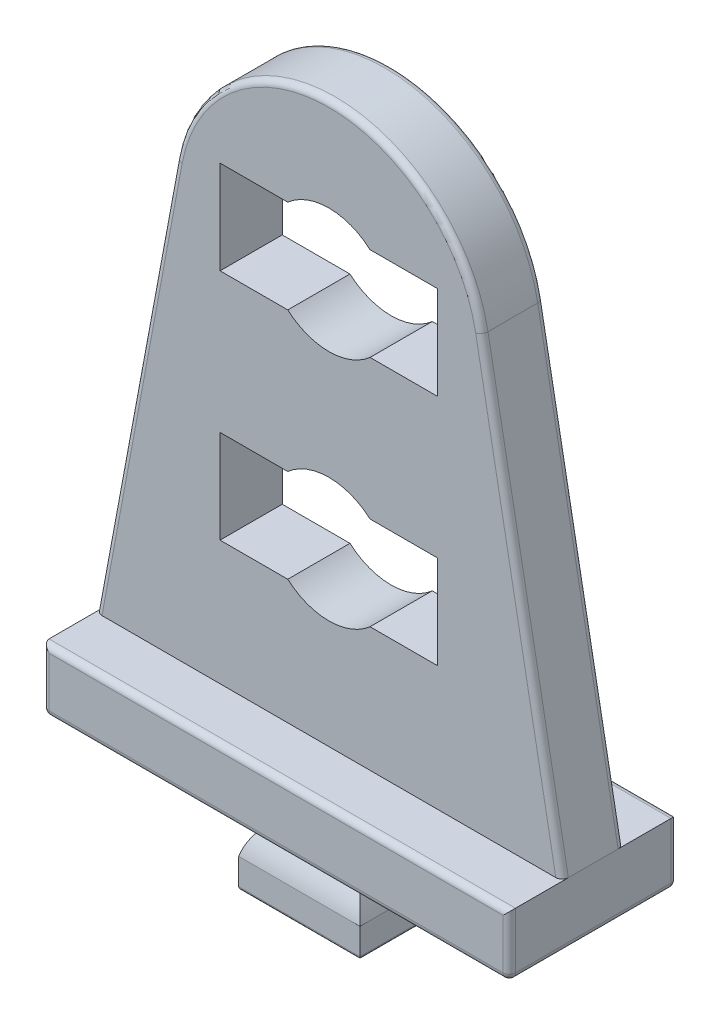
SolidWorks part; units mm, degrees
ref_plane "前视基准面" through (0, 0, 0) normal (0, 0, 1) x (1, 0, 0)
ref_plane "上视基准面" through (0, 0, 0) normal (0, 1, 0) x (1, 0, 0)
ref_plane "右视基准面" through (0, 0, 0) normal (1, 0, 0) x (0, 0, -1)
sketch "草图1" plane through (0, 0, 0) normal (0, 0, 1) x (1, 0, 0)
  line L0 (0, 0) -> (7.5, 0)
  line L1 (7.5, 0) -> (7.5, 2)
  line L2 (7.5, 2) -> (-7.5, 2)
  line L3 (-7.5, 2) -> (-7.5, 0)
  line L4 (-7.5, 0) -> (0, 0)
  dimension "D1" = 7.5
  dimension "D2" = 15
  dimension "D3" = 2
extrude "凸台-拉伸1" add sketch "草图1" along normal blind 2.7 and the other way blind 2.7
sketch "草图2" plane through (0, 0, 0) normal (0, 0, 1) x (1, 0, 0)
  line L0 (0, 2) -> (0, 7.5) construction
  line L1 (7.5, 2) -> (-7.5, 2) construction
  line L2 (0, 7.5) -> (0, 15) construction
  line L3 (0, 15) -> (0, 20) construction
  line L4 (-7.5, 2) -> (-4.9159, 15.913)
  line L5 (7.5, 2) -> (4.9159, 15.913)
  line L6 (-7.5, 2) -> (7.5, 2)
  arc A0 (4.9159, 15.913) -> (-4.9159, 15.913) centre (0, 15) ccw
  dimension "D1" = 5.5
  dimension "D2" = 7.5
  dimension "D3" = 5
extrude "凸台-拉伸2" add sketch "草图2" along normal blind 1 and the other way blind 1
sketch "草图3" plane through (0, 0, 1) normal (0, 0, 1) x (1, 0, 0)
  line L0 (0, 0) -> (0, 7.5) construction
  line L1 (3.5, 6) -> (3.5, 9)
  line L2 (3.5, 6) -> (1.3229, 6)
  line L3 (3.5, 9) -> (1.3229, 9)
  line L4 (-3.5, 6) -> (-3.5, 9)
  line L5 (3.5, 6) -> (-3.5, 9) construction
  line L6 (3.5, 9) -> (-3.5, 6) construction
  line L7 (-1.3229, 9) -> (-3.5, 9)
  line L8 (-1.3229, 6) -> (-3.5, 6)
  arc A0 (-1.3229, 6) -> (1.3229, 6) centre (0, 7.5) ccw
  arc A1 (1.3229, 9) -> (-1.3229, 9) centre (0, 7.5) ccw
  dimension "D2" = 4
  dimension "D1" = 7.5
  dimension "D3" = 3
  dimension "D4" = 7
extrude "切除-拉伸1" cut sketch "草图3" against normal through all
pattern_linear "阵列(线性)1" count 2 spacing 7.5 along (0, 1, 0) of "切除-拉伸1"
sketch "草图4" plane through (0, 0, 0) normal (0, 0, 1) x (1, 0, 0)
  line L0 (0, 0) -> (0, -2) construction
  line L1 (0, -2) -> (0, -2.5) construction
  line L2 (1.5, 0) -> (-1.5, 0)
  line L3 (-7.5, 0) -> (7.5, 0) construction
  line L4 (-1.5, 0) -> (-1.5, -0.6771)
  line L5 (1.95, -2.5) -> (-1.95, -2.5)
  line L6 (-1.95, -2.5) -> (-1.95, -1.5556)
  line L7 (1.95, -2.5) -> (1.95, -1.5556)
  line L8 (1.5, 0) -> (1.5, -0.6771)
  arc A0 (-1.5, -0.6771) -> (-1.95, -1.5556) centre (0, -2) ccw
  arc A1 (1.5, -0.6771) -> (1.95, -1.5556) centre (0, -2) cw
  dimension "D1" = 2
  dimension "D2" = 0.5
  dimension "D3" = 1.5
  dimension "D4" = 1.95
extrude "凸台-拉伸3" add sketch "草图4" along normal blind 2 and the other way blind 2
sketch "草图5" plane through (0, 0, 0) normal (1, 0, 0) x (0, 0, -1)
  line L0 (0, 0) -> (0, -2) construction
  line L1 (0, -2) -> (0, -2.5) construction
  line L2 (2, -2.5) -> (-2, -2.5) construction
  line L3 (0, 0) -> (1.5, 0) construction
  line L4 (1.5, 0) -> (1.5, -0.6771)
  line L5 (0, -2.5) -> (1.95, -2.5) construction
  line L6 (1.95, -2.5) -> (1.95, -1.5556)
  line L7 (1.95, -2.5) -> (2, -2.5)
  line L8 (2, -2.5) -> (2, 0)
  line L9 (2, 0) -> (1.5, 0)
  line L10 (-2, 0) -> (-1.5, 0)
  line L11 (-1.5, 0) -> (-1.5, -0.6771)
  line L12 (-2, -2.5) -> (-2, 0)
  line L13 (-1.95, -2.5) -> (-1.95, -1.5556)
  line L14 (-1.95, -2.5) -> (-2, -2.5)
  arc A0 (1.95, -1.5556) -> (1.5, -0.6771) centre (0, -2) ccw
  arc A1 (-1.95, -1.5556) -> (-1.5, -0.6771) centre (0, -2) cw
  dimension "D1" = 2
  dimension "D2" = 1.5
  dimension "D3" = 1.95
extrude "切除-拉伸2" cut sketch "草图5" against normal blind 2 and the other way blind 2
fillet "圆角1" radius 0.1 4 edges at (0, -2.5, -1.95) (-1.95, -2.5, 0) (0, -2.5, 1.95) (1.95, -2.5, 0)
fillet "圆角4" radius 0.2 8 edges at (-7.5, 1, 2.7) (0, 2, 2.7) (7.5, 1, 2.7) (0, 0, 2.7) (7.5, 1, -2.7) (0, 2, -2.7) (-7.5, 1, -2.7) (0, 0, -2.7)
fillet "圆角5" radius 0.2 6 edges at (-7.4414, 0.0586, -2.6414) (-7.4414, 0.0586, 2.6414) (7.4414, 0.0586, -2.6414) (7.4414, 0.0586, 2.6414) (-7.5, 0, 0) (7.5, 0, 0)
fillet "圆角7" radius 0.2 6 edges at (0, 20, 1) (0, 20, -1)
